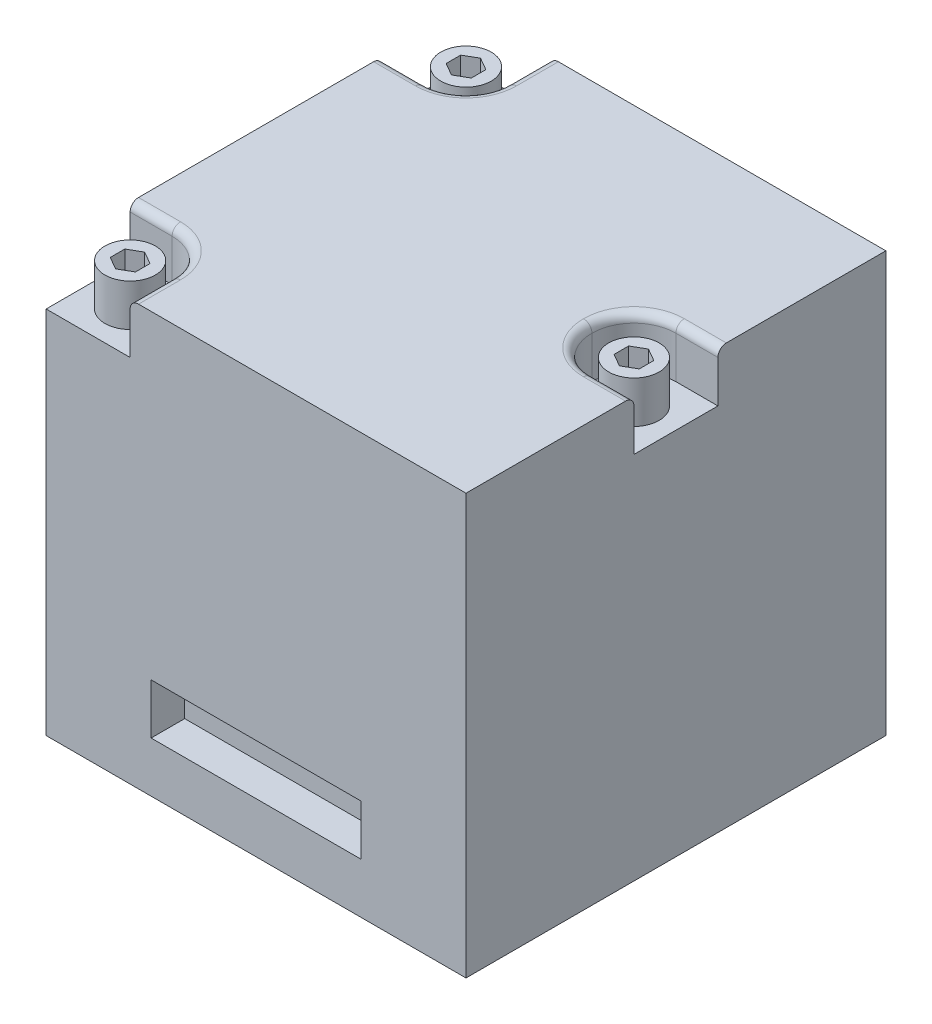
SolidWorks part; units mm, degrees
ref_plane "Front Plane" through (0, 0, 0) normal (0, 0, 1) x (1, 0, 0)
ref_plane "Top Plane" through (0, 0, 0) normal (0, 1, 0) x (1, 0, 0)
ref_plane "Right Plane" through (0, 0, 0) normal (1, 0, 0) x (0, 0, -1)
sketch "Sketch1" plane through (0, 0, 0) normal (0, 0, 1) x (1, 0, 0)
  line L5 (25, -25) -> (-25, -25)
  line L6 (25, -25) -> (25, 25)
  line L7 (25, 25) -> (-25, 25)
  line L8 (-25, -25) -> (-25, 25)
  line L9 (25, -25) -> (-25, 25) construction
  line L10 (25, 25) -> (-25, -25) construction
  point P0 (0, 0)
  dimension "D1" = 50
  dimension "D2" = 50
extrude "Boss-Extrude1" add sketch "Sketch1" along normal blind 50
sketch "Sketch2" plane through (0, 25, 0) normal (0, 1, 0) x (1, 0, 0)
  line L0 (25, -50) -> (25, 0) construction
  line L1 (-25, 0) -> (-15, 0)
  line L2 (-25, 0) -> (-25, -10)
  line L3 (-25, -10) -> (-15, -10)
  line L4 (-15, 0) -> (-15, -10)
  line L5 (-25, -50) -> (-15, -50)
  line L6 (-25, -50) -> (-25, -40)
  line L7 (-25, -40) -> (-15, -40)
  line L8 (-15, -50) -> (-15, -40)
  line L9 (25, -20) -> (15, -20)
  line L10 (25, -20) -> (25, -30)
  line L11 (25, -30) -> (15, -30)
  line L12 (15, -20) -> (15, -30)
  line L13 (25, 0) -> (-25, 0) construction
  dimension "D1" = 10
  dimension "D2" = 10
  dimension "D3" = 10
  dimension "D4" = 10
  dimension "D5" = 10
  dimension "D6" = 10
  dimension "D7" = 20
extrude "Cut-Extrude1" cut sketch "Sketch2" against normal blind 6
fillet "Fillet1" radius 5 4 edges at (15, 22, 30) (15, 22, 20) (-15, 22, 40) (-15, 22, 10)
fillet "Fillet2" radius 1 10 edges at (22.5, 25, 30) (16.4645, 25, 28.5355) (22.5, 25, 20) (-15, 25, 2.5) (-22.5, 25, 10) (-22.5, 25, 40) (-15, 25, 47.5) (16.4645, 25, 21.4645) (-16.4645, 25, 8.5355) (-16.4645, 25, 41.4645)
sketch "Sketch4" plane through (0, 19, 0) normal (0, 1, 0) x (1, 0, 0)
  line L0 (-25, 0) -> (-15, 0) construction
  line L1 (-25, 0) -> (-25, -10) construction
  line L2 (-25, -10) -> (-15, -10) construction
  line L3 (-15, 0) -> (-15, -10) construction
  line L4 (-25, -50) -> (-15, -50) construction
  line L5 (-25, -50) -> (-25, -40) construction
  line L6 (-25, -40) -> (-15, -40) construction
  line L7 (-15, -50) -> (-15, -40) construction
  line L8 (25, -20) -> (15, -20) construction
  line L9 (25, -20) -> (25, -30) construction
  line L10 (25, -30) -> (15, -30) construction
  line L11 (15, -20) -> (15, -30) construction
  line L14 (-15, 0) -> (-25, 0) construction
  line L15 (-25, 0) -> (-25, -10) construction
  line L16 (-25, -40) -> (-25, -50) construction
  line L17 (-25, -50) -> (-15, -50) construction
  line L18 (25, -30) -> (25, -20) construction
  line L19 (25, 0) -> (-14, 0) construction
  line L20 (-20, 0) -> (-20, -10) construction
  line L21 (-25, -5) -> (-15, -5) construction
  line L22 (-20, -40) -> (-20, -50) construction
  line L23 (-25, -45) -> (-15, -45) construction
  line L24 (20, -20) -> (20, -30) construction
  line L25 (25, -25) -> (15, -25) construction
  circle A0 centre (-20, -5) radius 3
  circle A1 centre (-20, -45) radius 3
  circle A2 centre (20, -25) radius 3
  dimension "D8" = 6
  dimension "D9" = 6
  dimension "D10" = 6
  dimension "D1" = 10
  dimension "D2" = 10
  dimension "D3" = 10
  dimension "D4" = 10
  dimension "D5" = 10
  dimension "D6" = 10
  dimension "D7" = 20
extrude "Boss-Extrude2" add sketch "Sketch4" along normal blind 5
sketch "Sketch5" plane through (0, 24, 0) normal (0, 1, 0) x (1, 0, 0)
  line L1 (-20, -3.2679) -> (-21.5, -4.134)
  line L2 (-21.5, -4.134) -> (-21.5, -5.866)
  line L3 (-21.5, -5.866) -> (-20, -6.7321)
  line L4 (-20, -6.7321) -> (-18.5, -5.866)
  line L5 (-18.5, -5.866) -> (-18.5, -4.134)
  line L6 (-18.5, -4.134) -> (-20, -3.2679)
  line L7 (-20, -43.2679) -> (-21.5, -44.134)
  line L8 (-21.5, -44.134) -> (-21.5, -45.866)
  line L9 (-21.5, -45.866) -> (-20, -46.7321)
  line L10 (-20, -46.7321) -> (-18.5, -45.866)
  line L11 (-18.5, -45.866) -> (-18.5, -44.134)
  line L12 (-18.5, -44.134) -> (-20, -43.2679)
  line L13 (20, -23.2679) -> (18.5, -24.134)
  line L14 (18.5, -24.134) -> (18.5, -25.866)
  line L15 (18.5, -25.866) -> (20, -26.7321)
  line L16 (20, -26.7321) -> (21.5, -25.866)
  line L17 (21.5, -25.866) -> (21.5, -24.134)
  line L18 (21.5, -24.134) -> (20, -23.2679)
  circle A0 centre (-20, -5) radius 1.5 construction
  circle A1 centre (-20, -45) radius 1.5 construction
  circle A2 centre (20, -25) radius 1.5 construction
  dimension "D1" = 3
  dimension "D2" = 3
  dimension "D3" = 3
extrude "Cut-Extrude2" cut sketch "Sketch5" against normal blind 4
sketch "Sketch6" plane through (0, 0, 50) normal (0, 0, 1) x (1, 0, 0)
  line L0 (0, 25) -> (0, -25) construction
  line L1 (25, 25) -> (-14, 25) construction
  line L2 (-25, -25) -> (25, -25) construction
  line L4 (-12.5, -19) -> (12.5, -19)
  line L5 (-12.5, -19) -> (-12.5, -13)
  line L6 (-12.5, -13) -> (12.5, -13)
  line L7 (12.5, -19) -> (12.5, -13)
  line L8 (-12.5, -19) -> (12.5, -13) construction
  line L9 (-12.5, -13) -> (12.5, -19) construction
  point P6 (0, -16)
  dimension "D1" = 6
  dimension "D2" = 25
  dimension "D3" = 6
extrude "Cut-Extrude3" cut sketch "Sketch6" against normal blind 4
